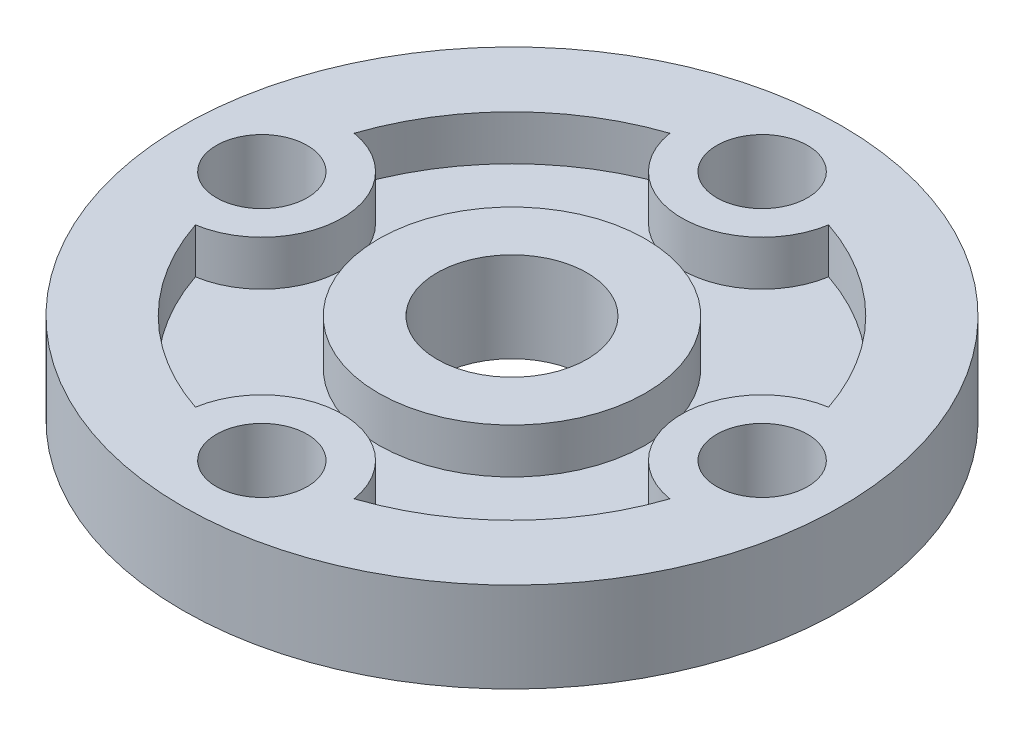
SolidWorks part; units mm, degrees
ref_plane "Front Plane" through (0, 0, 0) normal (0, 0, 1) x (1, 0, 0)
ref_plane "Top Plane" through (0, 0, 0) normal (0, 1, 0) x (1, 0, 0)
ref_plane "Right Plane" through (0, 0, 0) normal (1, 0, 0) x (0, 0, -1)
sketch "Sketch1" plane through (0, 0, 0) normal (0, 1, 0) x (1, 0, 0)
  circle A0 centre (0, 0) radius 73.2148
  circle A1 centre (0, 0) radius 55.576
  circle A3 centre (0, 0) radius 29.6677
  circle A5 centre (0, 0) radius 16.6611
  circle A7 centre (55.576, 0) radius 17.8676
  circle A8 centre (55.576, 0) radius 10.089
  circle A9 centre (0, -55.576) radius 10.089
  circle A10 centre (0, -55.576) radius 17.8676
  circle A11 centre (-55.576, 0) radius 10.089
  circle A12 centre (-55.576, 0) radius 17.8676
  circle A13 centre (0, 55.576) radius 10.089
  circle A14 centre (0, 55.576) radius 17.8676
  dimension "D1" = 4
extrude "Boss-Extrude4" add sketch "Sketch1" against normal blind 20 contours A0
extrude "Cut-Extrude2" cut sketch "Sketch1<7>" against normal blind 20 contours A5 | A11 | A13 | A8 | A9 region at (0, 0, 0)
sketch "Sketch1<7>" plane through (0, 0, 0) normal (0, 1, 0) x (1, 0, 0) same geometry as "Sketch1"
extrude "Cut-Extrude3" cut sketch "Sketch1<8>" against normal blind 10 contours A14 A1 A12 A10 A7 A3 region at (36.2178, 0, 0)
sketch "Sketch1<8>" plane through (0, 0, 0) normal (0, 1, 0) x (1, 0, 0) same geometry as "Sketch1"
